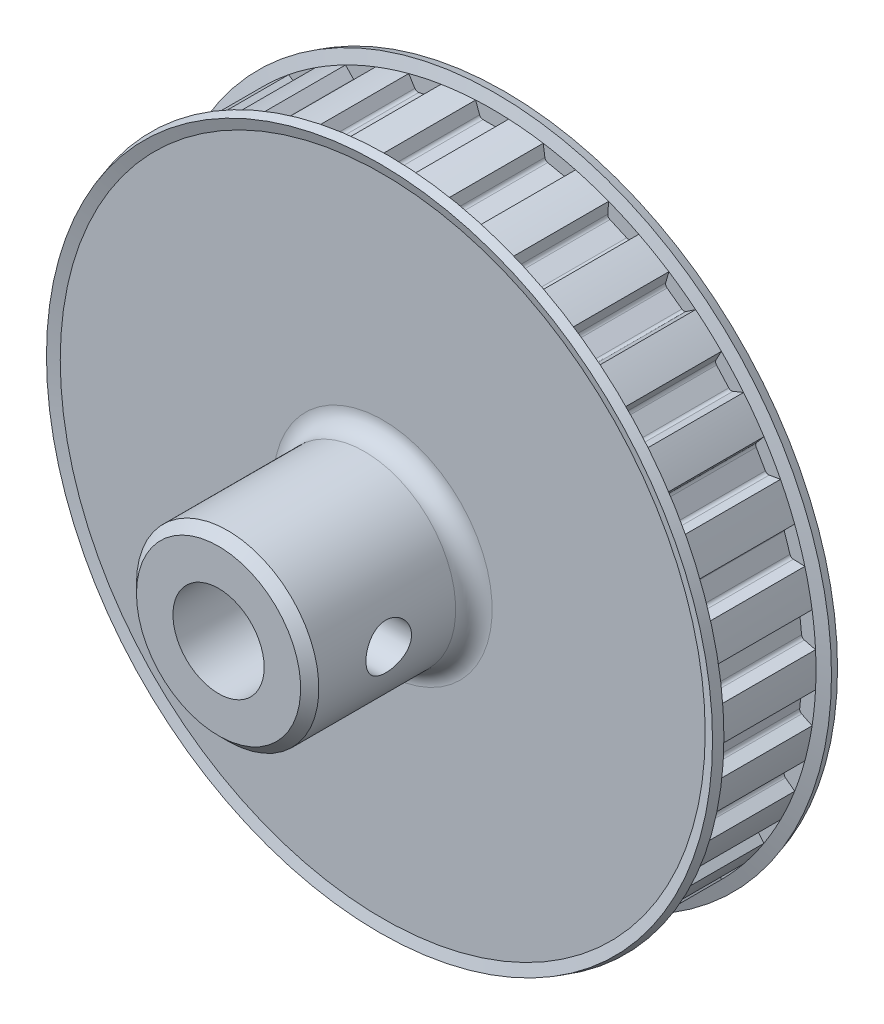
SolidWorks part; units mm, degrees
material "6061-T6 (SS)"
ref_plane "Plane1" through (0, 0, 0) normal (0, 0, 1) x (1, 0, 0)
ref_plane "Plane2" through (0, 0, 0) normal (0, 1, 0) x (1, 0, 0)
ref_plane "Plane3" through (0, 0, 0) normal (1, 0, 0) x (0, 0, -1)
sketch "Clipboard" plane through (0, 0, 0) normal (0, 0, 1) x (1, 0, 0)
  line L0 (0, 0) -> (14.224, 0)
  line L1 (0, 0) -> (32.9956, 19.05)
  line L2 (0, 0) -> (32.9956, -19.05)
  dimension "Overall_len" = 38.1
  dimension "T_dim" = 14.224
  dimension "OAL" = 38.1
  dimension "Show_grvs" = 30
  dimension "Num_grvs" = 30
sketch "Sketch1" plane through (0, 0, 0) normal (0, 0, 1) x (1, 0, 0)
  circle A0 centre (0, 0) radius 45.0977
  dimension "Outside_dia" = 90.1954
extrude "BasePulley" add sketch "Sketch1" against normal blind 13.97
sketch "Sketch2" plane through (0, 0, 0) normal (1, 0, 0) x (0, 0, -1)
  line L0 (13.97, 45.0977) -> (14.4748, 46.7487)
  line L1 (14.4748, 46.7487) -> (15.6893, 46.3774)
  line L2 (6.985, 0) -> (6.985, 66.675) construction
  line L3 (15.6893, 46.3774) -> (15.24, 44.9079)
  line L4 (15.24, 44.9079) -> (15.24, 0)
  line L5 (0, 45.0977) -> (-0.5048, 46.7487)
  line L6 (13.97, -45.0977) -> (13.97, 45.0977) construction
  line L7 (-0.5048, 46.7487) -> (-1.7193, 46.3774)
  line L8 (-1.7193, 46.3774) -> (-1.27, 44.9079)
  line L9 (-1.27, 44.9079) -> (-1.27, 0)
  line L10 (13.97, 45.0977) -> (0, 45.0977)
  line L11 (0, 0) -> (38.2092, 0) construction
  line L12 (13.97, 0) -> (0, 0) construction
  line L13 (-1.27, 0) -> (15.24, 0)
  dimension "D1" = 6.985
  dimension "Flange_ang" = 17
  dimension "Flange_thickness" = 1.27
  dimension "D2" = 45.0977
  dimension "Flange_ht" = 1.651
  dimension "D3" = 1.27
revolve "Flange" add sketch "Sketch2" angle 360 about L11
ref_plane "Plane4" through (0, 0, -6.985) normal (0, 0, 1) x (1, 0, 0)
sketch "Sketch3" plane through (0, 0, -6.985) normal (0, 0, 1) x (1, 0, 0)
  line L0 (-2.3241, 45.0977) -> (-2.3241, 70.4977)
  line L1 (2.3241, 45.0977) -> (2.3241, 70.4977)
  line L2 (0, 0) -> (0, 45.0977) construction
  line L3 (-2.3241, 45.0977) -> (2.3241, 45.0977) construction
  line L4 (-1.275, 43.1927) -> (1.275, 43.1927)
  line L5 (2.3241, 45.0977) -> (1.7524, 43.527)
  line L6 (-2.3241, 45.0977) -> (-1.7524, 43.527)
  line L7 (2.3241, 70.4977) -> (-2.3241, 70.4977)
  arc A0 (1.275, 43.1927) -> (1.7524, 43.527) centre (1.275, 43.7007) ccw
  arc A2 (-1.7524, 43.527) -> (-1.275, 43.1927) centre (-1.275, 43.7007) ccw
  dimension "Grv_rad_bot" = 0.508
  dimension "D4" = 25.4
  dimension "D1" = 45.0977
  dimension "Grv_ang" = 40
  dimension "Grv_width" = 4.6482
  dimension "D3" = 20
  dimension "Grv_depth" = 1.905
extrude "Groove" cut sketch "Sketch3" against normal mid plane 13.97
pattern_circular "Grooves" count 30 every 12 about axis through (0, 0, -13.97) along (0, 0, 1) of "Groove"
sketch "Sketch4" plane through (0, 0, 0) normal (1, 0, 0) x (0, 0, -1)
  line L0 (0, 0) -> (47.6781, 0) construction
  line L1 (13.97, 0) -> (0, 0) construction
  line L2 (0, 0) -> (-24.13, 0)
  line L3 (-24.13, 0) -> (-24.13, 12.7)
  line L4 (-24.13, 12.7) -> (0, 12.7)
  line L5 (0, 12.7) -> (0, 0)
  line L6 (-24.13, -12.7) -> (0, -12.7) construction
  dimension "Hub_dia" = 25.4
  dimension "Hub_depth" = 24.13
revolve "BaseHub" add sketch "Sketch4" angle 360 about L0
sketch "BorSke" plane through (0, 0, 24.13) normal (0, 0, 1) x (1, 0, 0)
  circle A0 centre (0, 0) radius 6.35
  dimension "Diameter" = 12.7
extrude "Bore" cut sketch "BorSke" against normal through all
sketch "KeySke" plane through (0, 0, 24.13) normal (0, 0, 1) x (1, 0, 0)
  line L0 (1.5875, 7.874) -> (1.5875, 0)
  line L1 (1.5875, 7.874) -> (-1.5875, 7.874)
  line L2 (-1.5875, 7.874) -> (-1.5875, 0)
  line L3 (-1.5875, 0) -> (1.5875, 0)
  line L4 (0, 31.75) -> (0, -3.175) construction
  dimension "Width" = 3.175
  dimension "Offset" = 7.874
extrude "Keyway" [suppressed] cut sketch "KeySke" against normal through all
pattern_circular "Keyway2" [suppressed] count 2 every 90
sketch "Sketch5" plane through (0, 0, 0) normal (1, 0, 0) x (0, 0, -1)
  line L0 (-24.13, 0) -> (-2.1351, 0) construction
  line L1 (-24.13, 12.7) -> (-24.13, -12.7) construction
  circle A0 centre (-13.1325, 0) radius 3.175
  dimension "D1" = 6.35
extrude "Cut-Extrude1" cut sketch "Sketch5" against normal through all and the other way through all
fillet "Fillet1" radius 2.54 1 edges at (-12.7, 0, 1.27)
chamfer "Chamfer1" distance 1.27 angle 45 1 edges at (12.7, 0, 24.13)
equation "\"D1@Plane4\" = \"Width@BasePulley\" / 2"
equation "\"D1@Groove\" = \"Width@BasePulley\""
equation "\"D1@Sketch3\" = \"Outside_dia@Sketch1\" / 2"
equation "\"D1@Sketch2\" = \"Width@BasePulley\" / 2"
equation "\"D2@Sketch2\" = \"Outside_dia@Sketch1\" / 2"
equation "\"D3@Sketch2\" = \"Flange_thickness@Sketch2\""
equation "\"Num_grvs@Clipboard\" = int( \"Num_grvs@Clipboard\" )"
equation "\"Show_grvs@Clipboard\" = int( \"Show_grvs@Clipboard\" )"
equation "\"Show_grvs@Clipboard\" = ((sgn( \"Show_grvs@Clipboard\" - \"Num_grvs@Clipboard\" )-1)*( \"Show_grvs@Clipboard\" - \"Num_grvs@Clipboard\" ))/-2+ \"Num_grvs@Clipboard\""
equation "\"Show_grvs@Clipboard\" = ((sgn( \"Show_grvs@Clipboard\" - 1.0)+1)*( \"Show_grvs@Clipboard\" - 1.0))/2 +1.0"
equation "\"Angle@Grooves\" = 360.0 / \"Num_grvs@Clipboard\""
equation "\"Num_grvs@Grooves\" =  \"Show_grvs@Clipboard\""
equation "\"Offset@KeySke\" = \"T_dim@Clipboard\" - \"Diameter@BorSke\" / 2.0"
equation "\"OAL@Clipboard\" = \"Overall_len@Clipboard\""
equation "\"Hub_depth@Sketch4\" = \"OAL@Clipboard\" - \"Width@BasePulley\""
